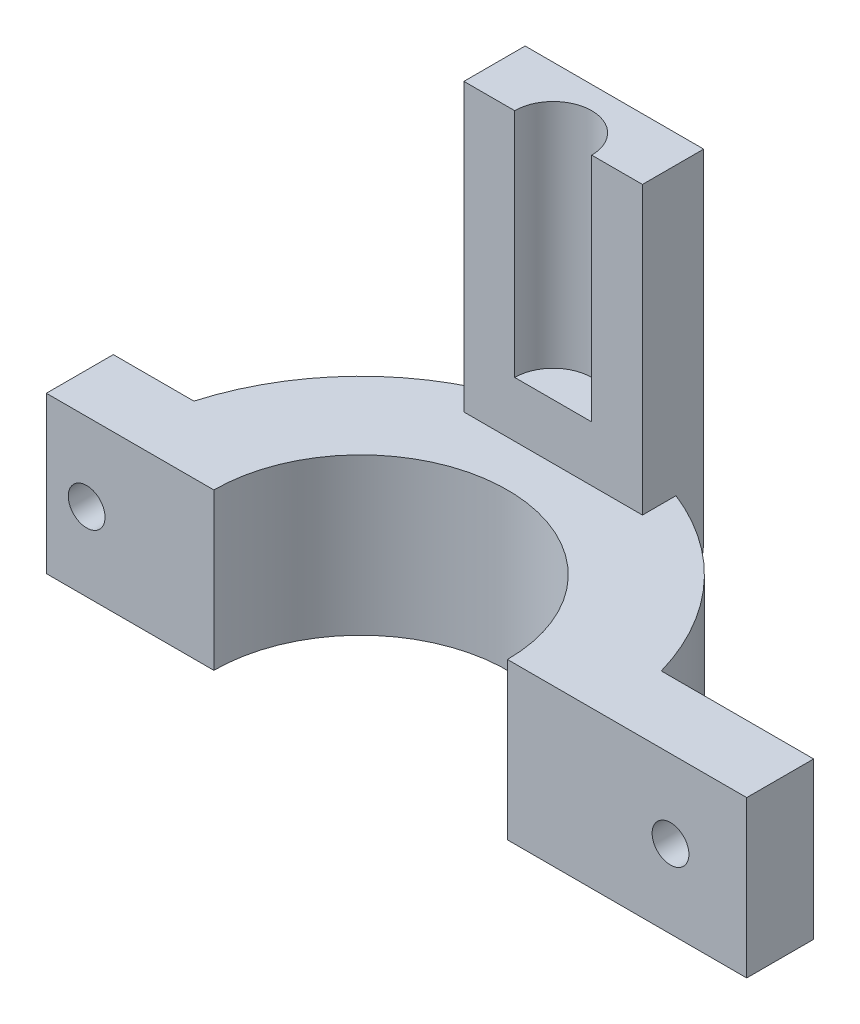
SolidWorks part; units mm, degrees
ref_plane "前基準面" through (0, 0, 0) normal (0, 0, 1) x (1, 0, 0)
ref_plane "上基準面" through (0, 0, 0) normal (0, 1, 0) x (1, 0, 0)
ref_plane "右基準面" through (0, 0, 0) normal (1, 0, 0) x (0, 0, -1)
sketch "草圖1" plane through (0, 0, 0) normal (0, 1, 0) x (1, 0, 0)
  line L1 (-15.75, 7.075) -> (15.75, 7.075)
  line L2 (-15.75, 7.075) -> (-15.75, -7.075)
  line L3 (-15.75, -7.075) -> (15.75, -7.075)
  line L4 (15.75, 7.075) -> (15.75, -7.075)
  line L5 (-15.75, 7.075) -> (15.75, -7.075) construction
  line L6 (-15.75, -7.075) -> (15.75, 7.075) construction
  point P0 (0, 0)
  dimension "D1" = 14.15
  dimension "D2" = 31.5
extrude "伸長-薄件1" add sketch "草圖1" along normal blind 12.25 thin thin type one direction wall 10
sketch "草圖2" plane through (0, 12.25, 0) normal (0, 1, 0) x (1, 0, 0)
  line L0 (-1014.255, 0) -> (48985.745, 0) construction
  line L1 (-15.75, 7.075) -> (-15.75, -7.075) construction
  line L2 (-20.75, -988.4004) -> (-20.75, 49011.5996) construction
  line L3 (-25.75, 17.075) -> (-20.75, 17.075) construction
  line L4 (-25.75, 17.075) -> (-25.75, 11.5996) construction
  line L5 (-25.75, 11.5996) -> (-20.75, 11.5996) construction
  line L6 (-20.75, 17.075) -> (-20.75, 11.5996) construction
  line L7 (25.75, 17.075) -> (20.75, 17.075) construction
  line L8 (25.75, 17.075) -> (25.75, 12.4477) construction
  line L9 (25.75, 12.4477) -> (20.75, 12.4477) construction
  line L10 (20.75, 17.075) -> (20.75, 12.4477) construction
  line L11 (20.75, -987.5523) -> (20.75, 49012.4477) construction
  circle A0 centre (-20.75, 0) radius 1.91
  circle A1 centre (20.75, 0) radius 1.91
  point P5 (-15.75, 0)
  dimension "D3" = 3.82
  dimension "D4" = 3.82
  dimension "D1" = 5
  dimension "D2" = 5
extrude "除料-伸長1" cut sketch "草圖2" against normal through all
sketch "草圖4" plane through (0, 0, 0) normal (0, -1, 0) x (1, 0, 0)
  line L0 (-1000, 0) -> (49000, 0) construction
  line L1 (25.75, 17.075) -> (25.75, -17.075) construction
  line L2 (12.75, 6.955) -> (25.75, 6.955)
  line L3 (12.75, 6.955) -> (12.75, -6.955)
  line L4 (12.75, -6.955) -> (25.75, -6.955)
  line L5 (25.75, 6.955) -> (25.75, -6.955)
  line L6 (12.75, 6.955) -> (25.75, -6.955) construction
  line L7 (12.75, -6.955) -> (25.75, 6.955) construction
  point P1 (19.25, 0)
  dimension "D1" = 13.91
  dimension "D2" = 13
extrude "填料-伸長1" add sketch "草圖4" along normal blind 74.82
sketch "草圖5" plane through (12.75, 0, 0) normal (-1, 0, 0) x (0, 0, 1)
  line L0 (6.955, -74.82) -> (6.955, 0) construction
  line L1 (-6.955, -74.82) -> (6.955, -74.82)
  line L2 (-6.955, -74.82) -> (-6.955, -58.59)
  line L3 (-6.955, -58.59) -> (6.955, -58.59)
  line L4 (6.955, -74.82) -> (6.955, -58.59)
  dimension "D1" = 16.23
extrude "填料-伸長2" add sketch "草圖5" along normal blind 16
sketch "草圖7" plane through (3.6267, -74.82, 0) normal (0, -1, 0) x (1, 0, 0)
  circle A0 centre (-30.9782, 0) radius 15.25
  dimension "D1" = 30.5
extrude "伸長-薄件2" add sketch "草圖7" against normal blind 16.23 thin thin type one direction wall 10
ref_plane "平面1" through (-60, 0, 0) normal (1, 0, 0) x (0, 0, -1)
ref_plane "平面2" through (-55, 0, 0) normal (1, 0, 0) x (0, 0, -1)
ref_plane "平面3" through (-60, 0, 0) normal (1, 0, 0) x (0, 0, -1)
sketch "草圖15" plane through (0, 0, -6.955) normal (0, 0, -1) x (-1, 0, 0)
  line L0 (-996.9218, -66.705) -> (49003.0782, -66.705) construction
  line L1 (3.0782, -74.82) -> (3.0782, -58.59) construction
  line L2 (-4.8359, -1058.59) -> (-4.8359, 48941.41) construction
  line L3 (3.0782, -58.59) -> (-12.75, -58.59) construction
  circle A0 centre (-4.8359, -66.705) radius 1.91
  point P5 (3.0782, -66.705)
  point P10 (-4.8359, -58.59)
  dimension "D1" = 3.82
extrude "除料-伸長6" cut sketch "草圖15" against normal through all
ref_plane "平面4" through (-60, 0, 0) normal (1, 0, 0) x (0, 0, -1)
sketch "草圖16" plane through (-60, 0, 0) normal (1, 0, 0) x (0, 0, -1)
  line L1 (6.955, -58.59) -> (-6.955, -58.59)
  line L2 (6.955, -58.59) -> (6.955, -74.82)
  line L3 (6.955, -74.82) -> (-6.955, -74.82)
  line L4 (-6.955, -58.59) -> (-6.955, -74.82)
extrude "填料-伸長4" add sketch "草圖16" along normal blind 10
sketch "草圖17" plane through (0, 0, -6.955) normal (0, 0, -1) x (-1, 0, 0)
  line L0 (-948.3753, -66.705) -> (49051.6247, -66.705) construction
  line L1 (51.6247, -74.82) -> (51.6247, -58.59) construction
  line L2 (55.8124, -1058.59) -> (55.8124, 48941.41) construction
  line L3 (51.6247, -58.59) -> (60, -58.59) construction
  circle A0 centre (55.8124, -66.705) radius 1.91
  point P5 (51.6247, -66.705)
  point P10 (55.8124, -58.59)
  dimension "D1" = 3.82
extrude "除料-伸長7" cut sketch "草圖17" against normal through all
sketch "草圖19" plane through (0, -58.59, 0) normal (0, 1, 0) x (1, 0, 0)
  line L0 (-60, 6.955) -> (-60, -6.955) construction
  line L1 (-60, 0) -> (36.5445, 0)
  line L2 (-60, 0) -> (-60, -28.4267)
  line L3 (-60, -28.4267) -> (36.5445, -28.4267)
  line L4 (36.5445, 0) -> (36.5445, -28.4267)
extrude "除料-伸長8" cut sketch "草圖19" against normal blind 41 and the other way blind 83
sketch "草圖21" plane through (25.75, 0, 0) normal (1, 0, 0) x (0, 0, -1)
  line L0 (0, -74.82) -> (0, 12.25) construction
  line L1 (0, -36.2363) -> (18.5662, -36.2363)
  line L2 (0, -36.2363) -> (0, 14.4577)
  line L3 (0, 14.4577) -> (18.5662, 14.4577)
  line L4 (18.5662, -36.2363) -> (18.5662, 14.4577)
extrude "除料-伸長10" cut sketch "草圖21" against normal blind 57
sketch "草圖22" plane through (0, -36.2363, 0) normal (0, 1, 0) x (1, 0, 0)
  line L1 (12.75, 0) -> (25.75, 0)
  line L2 (12.75, 0) -> (12.75, 6.955)
  line L3 (12.75, 6.955) -> (25.75, 6.955)
  line L4 (25.75, 0) -> (25.75, 6.955)
extrude "除料-伸長11" cut sketch "草圖22" against normal blind 57
ref_plane "平面5" through (0, 0, -30) normal (0, 0, 1) x (1, 0, 0)
sketch "草圖23" plane through (0, 0, -30) normal (0, 0, 1) x (1, 0, 0)
  line L0 (-27.3515, -1058.59) -> (-27.3515, 48941.41) construction
  line L1 (-3.0782, -58.59) -> (-51.6247, -58.59) construction
  line L2 (-3.0782, -74.82) -> (-3.0782, -58.59) construction
  line L3 (-18.0782, -28.8448) -> (-36.6247, -28.8448)
  line L4 (-18.0782, -28.8448) -> (-18.0782, -71.3448)
  line L5 (-18.0782, -71.3448) -> (-36.6247, -71.3448)
  line L6 (-36.6247, -28.8448) -> (-36.6247, -71.3448)
  line L7 (-51.6247, -74.82) -> (-51.6247, -58.59) construction
  point P5 (-27.3515, -58.59)
  dimension "D1" = 15
  dimension "D2" = 15
  dimension "D3" = 42.5
extrude "填料-伸長6" add sketch "草圖23" along normal blind 10 and the other way blind 5
sketch "草圖24" plane through (0, -28.8448, 0) normal (0, 1, 0) x (1, 0, 0)
  line L0 (-18.0782, 20) -> (-36.6247, 20) construction
  circle A0 centre (-27.3515, 20) radius 4
  dimension "D1" = 8
extrude "除料-伸長12" cut sketch "草圖24" against normal blind 24
sketch "草圖26" plane through (0, -28.8448, 0) normal (0, 1, 0) x (1, 0, 0)
  line L0 (-36.6247, 35) -> (-36.6247, 20) construction
  line L1 (-18.0782, 35) -> (-36.6247, 35)
  line L2 (-18.0782, 35) -> (-18.0782, 26.3584)
  line L3 (-18.0782, 26.3584) -> (-36.6247, 26.3584)
  line L4 (-36.6247, 35) -> (-36.6247, 26.3584)
extrude "除料-伸長13" cut sketch "草圖26" against normal through all
fillet "圓角1" radius 10 1 edges at (-27.3515, -71.3448, -26.3584)
